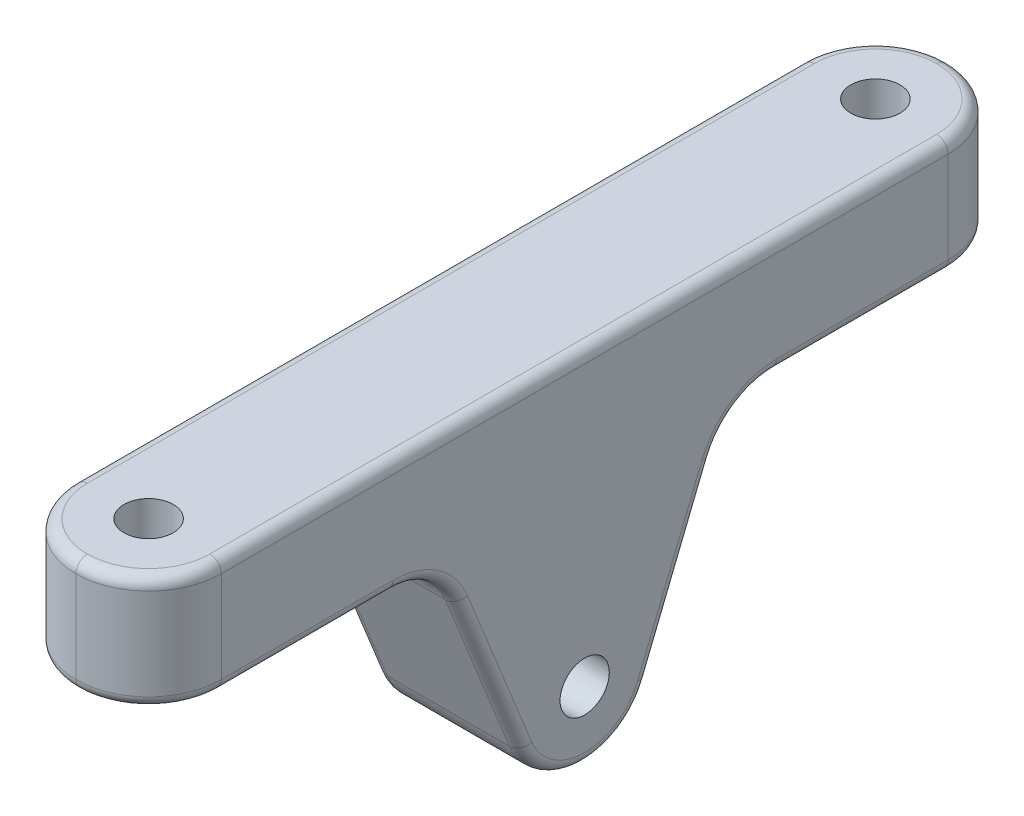
SolidWorks part; units mm, degrees
ref_plane "Front Plane" through (0, 0, 0) normal (0, 0, 1) x (1, 0, 0)
ref_plane "Top Plane" through (0, 0, 0) normal (0, 1, 0) x (1, 0, 0)
ref_plane "Right Plane" through (0, 0, 0) normal (1, 0, 0) x (0, 0, -1)
sketch "Sketch1" plane through (0, 0, 0) normal (1, 0, 0) x (0, 0, -1)
  line L0 (-38.1, 25.4) -> (38.1, 25.4)
  line L1 (-38.1, 25.4) -> (-38.1, 15.4)
  line L2 (-38.1, 15.4) -> (-12.7, 15.4)
  line L3 (-12.7, 15.4) -> (0, -16.0037)
  line L4 (0, -16.0037) -> (12.7, 15.4)
  line L5 (12.7, 15.4) -> (38.1, 15.4)
  line L6 (38.1, 15.4) -> (38.1, 25.4)
  circle A0 centre (0, 0) radius 2.15
  point P14 (0, 25.4)
  dimension "D1" = 4.3
  dimension "D2" = 25.4
  dimension "D3" = 10
  dimension "D4" = 38.1
  dimension "D5" = 6
  dimension "D6" = 25.4
extrude "Boss-Extrude1" add sketch "Sketch1" along normal blind 12.7
fillet "Fillet1" radius 6 3 edges at (6.35, 15.4, -12.7) (6.35, 15.4, 12.7) (6.35, -16.0037, 0)
fillet "Fillet2" radius 6.35 4 edges at (0, 20.4, -38.1) (12.7, 20.4, -38.1) (0, 20.4, 38.1) (12.7, 20.4, 38.1)
sketch "Sketch2" plane through (0, 25.4, 0) normal (0, 1, 0) x (1, 0, 0)
  circle A0 centre (6.35, -31.75) radius 2.15
  circle A1 centre (6.35, 31.75) radius 2.15
  arc A2 (6.35, 38.1) -> (0, 31.75) centre (6.35, 31.75) ccw construction
  arc A3 (6.35, 38.1) -> (0, 31.75) centre (6.35, 31.75) ccw
  arc A4 (0, -31.75) -> (6.35, -38.1) centre (6.35, -31.75) ccw construction
  arc A5 (0, -31.75) -> (6.35, -38.1) centre (6.35, -31.75) ccw
  dimension "D1" = 4.3
extrude "Cut-Extrude1" cut sketch "Sketch2" against normal up to next contours A0 | A1 region at (6.35, 25.4, 31.75) region at (6.35, 25.4, -31.75)
sketch "Sketch3" plane through (0, 0, 0) normal (-1, 0, 0) x (0, 0, 1)
  line L1 (0, 4.7343) -> (-4.1, 2.3671)
  line L2 (-4.1, 2.3671) -> (-4.1, -2.3671)
  line L3 (-4.1, -2.3671) -> (0, -4.7343)
  line L4 (0, -4.7343) -> (4.1, -2.3671)
  line L5 (4.1, -2.3671) -> (4.1, 2.3671)
  line L6 (4.1, 2.3671) -> (0, 4.7343)
  circle A0 centre (0, 0) radius 4.1 construction
  dimension "D1" = 8.2
extrude "Cut-Extrude2" cut sketch "Sketch3" against normal blind 4
fillet "Fillet3" radius 1 24 edges at (10.8401, 25.4, -36.2401) (1.8599, 25.4, -36.2401) (0, 25.4, 0) (1.8599, 25.4, 36.2401) (10.8401, 25.4, 36.2401) (12.7, 14.3748, 13.3913) (12.7, 15.4, 24.2478) (10.8401, 15.4, 36.2401) (1.8599, 15.4, 36.2401) (0, 15.4, 24.2478) (0, 14.3748, 13.3913) (0, 4.7, 8.3728) (0, -6, 0) (0, 4.7, -8.3728) (0, 14.3748, -13.3913) (0, 15.4, -24.2478) (1.8599, 15.4, -36.2401) (10.8401, 15.4, -36.2401) (12.7, 15.4, -24.2478) (12.7, 14.3748, -13.3913) (12.7, 4.7, -8.3728) (12.7, -6, 0) (12.7, 25.4, 0) (12.7, 4.7, 8.3728)
